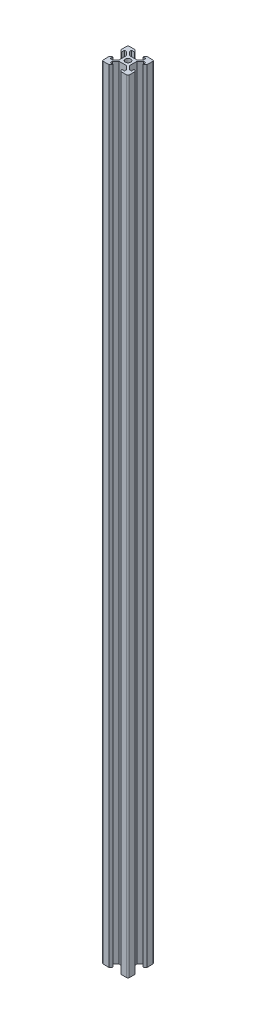
SolidWorks part; units mm, degrees
ref_plane "Front Plane" through (0, 0, 0) normal (0, 0, 1) x (1, 0, 0)
ref_plane "Top Plane" through (0, 0, 0) normal (0, 1, 0) x (1, 0, 0)
ref_plane "Right Plane" through (0, 0, 0) normal (1, 0, 0) x (0, 0, -1)
sketch "Sketch1" plane through (0, 0, 0) normal (0, 1, 0) x (1, 0, 0)
  line L0 (-3.125, 8.2) -> (-4.58, 10)
  line L1 (-9, 10) -> (9, 10)
  line L2 (-10, 9) -> (-10, -9)
  line L3 (-9, -10) -> (9, -10)
  line L4 (10, 9) -> (10, -9)
  line L5 (-10, 10) -> (10, -10) construction
  line L6 (-10, -10) -> (10, 10) construction
  line L7 (-10, 0) -> (0, 0) construction
  line L8 (0, 10) -> (0, 0) construction
  line L9 (-8.2, 3.125) -> (-10, 4.58)
  line L10 (-8.2, 3.125) -> (-8.2, 5.5)
  line L11 (-3.125, 8.2) -> (-5.5, 8.2)
  line L12 (-5.5, 8.2) -> (-5.5, 6.56)
  line L13 (-2.84, 3.9) -> (2.84, 3.9)
  line L14 (-5.5, 6.56) -> (-2.84, 3.9)
  line L15 (-8.2, 5.5) -> (-6.56, 5.5)
  line L16 (-6.56, 5.5) -> (-3.9, 2.84)
  line L17 (-3.9, 2.84) -> (-3.9, -2.84)
  line L18 (3.9, 2.84) -> (3.9, -2.84)
  line L19 (6.56, 5.5) -> (3.9, 2.84)
  line L20 (8.2, 5.5) -> (6.56, 5.5)
  line L21 (8.2, 3.125) -> (8.2, 5.5)
  line L22 (8.2, 3.125) -> (10, 4.58)
  line L23 (3.125, 8.2) -> (4.58, 10)
  line L24 (3.125, 8.2) -> (5.5, 8.2)
  line L25 (5.5, 8.2) -> (5.5, 6.56)
  line L26 (5.5, 6.56) -> (2.84, 3.9)
  line L27 (-8.2, -3.125) -> (-10, -4.58)
  line L28 (-8.2, -3.125) -> (-8.2, -5.5)
  line L29 (-8.2, -5.5) -> (-6.56, -5.5)
  line L30 (-6.56, -5.5) -> (-3.9, -2.84)
  line L31 (8.2, -3.125) -> (10, -4.58)
  line L32 (8.2, -3.125) -> (8.2, -5.5)
  line L33 (8.2, -5.5) -> (6.56, -5.5)
  line L34 (6.56, -5.5) -> (3.9, -2.84)
  line L35 (5.5, -6.56) -> (2.84, -3.9)
  line L36 (5.5, -8.2) -> (5.5, -6.56)
  line L37 (3.125, -8.2) -> (5.5, -8.2)
  line L38 (3.125, -8.2) -> (4.58, -10)
  line L39 (-5.5, -6.56) -> (-2.84, -3.9)
  line L40 (-2.84, -3.9) -> (2.84, -3.9)
  line L41 (-5.5, -8.2) -> (-5.5, -6.56)
  line L42 (-3.125, -8.2) -> (-5.5, -8.2)
  line L43 (-3.125, -8.2) -> (-4.58, -10)
  circle A0 centre (0, 0) radius 2.1
  arc A1 (-10, -9) -> (-9, -10) centre (-9, -9) ccw
  arc A2 (9, -10) -> (10, -9) centre (9, -9) ccw
  arc A3 (9, 10) -> (10, 9) centre (9, 9) cw
  arc A4 (-9, 10) -> (-10, 9) centre (-9, 9) ccw
  point P0 (0, 0)
  point P35 (0, 3.9)
  point P40 (-3.9, 0)
  point P41 (3.9, 0)
  dimension "D3" = 4.2
  dimension "D2" = 1
  dimension "D1" = 20
  dimension "D4" = 6.1
  dimension "D5" = 6.25
  dimension "D6" = 11
  dimension "D7" = 5.68
  dimension "D8" = 9.16
  dimension "D9" = 1.8
extrude "Boss-Extrude1" add sketch "Sketch1" along normal blind 600 contours L43 L42 L41 L39 L40 L35 L36 L37 L38 L3 L4 L31 L32 L33 L34 L18 L19 L20 L21 L22 L1 L23 L24 L25 L26 L13 L14 L12 L11 L0 L2 L9 L10 L15 L16 L17 L30 L29 L28 L27 A0 region at (-4.3125, 0, -8.4828)
